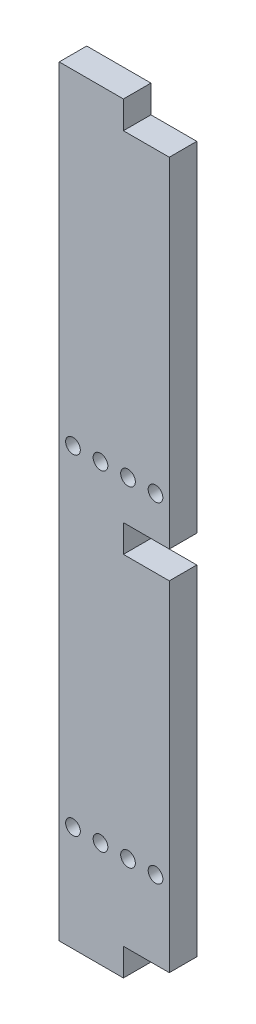
SolidWorks part; units mm, degrees
ref_plane "Plan de face" through (0, 0, 0) normal (0, 0, 1) x (1, 0, 0)
ref_plane "Plan de dessus" through (0, 0, 0) normal (0, 1, 0) x (1, 0, 0)
ref_plane "Plan de droite" through (0, 0, 0) normal (1, 0, 0) x (0, 0, -1)
sketch "Esquisse1" plane through (0, 0, 0) normal (0, 0, 1) x (1, 0, 0)
  line L0 (-6, 0) -> (6, 0)
  line L1 (6, 0) -> (6, 118) construction
  line L2 (6, 118) -> (-6, 118)
  line L3 (-6, 118) -> (-6, 0)
  line L4 (0, 118) -> (0, 0) construction
  line L10 (6, 100.5) -> (1, 100.5)
  line L11 (1, 100.5) -> (1, 97.5)
  line L12 (1, 97.5) -> (6, 97.5)
  line L13 (6, 97.5) -> (6, 60.5)
  line L14 (6, 60.5) -> (1, 60.5)
  line L15 (1, 60.5) -> (1, 57.5)
  line L16 (1, 57.5) -> (6, 57.5)
  line L17 (6, 57.5) -> (6, 20.5)
  line L18 (6, 20.5) -> (1, 20.5)
  line L19 (1, 20.5) -> (1, 17.5)
  line L20 (1, 17.5) -> (6, 17.5)
  line L25 (6, 17.5) -> (6, 0)
  line L26 (1, 99) -> (6, 99) construction
  line L27 (1, 59) -> (6, 59) construction
  line L28 (1, 19) -> (6, 19) construction
  line L32 (3.5, 298) -> (3.5, 99) construction
  line L33 (3.5, 99) -> (3.5, 59) construction
  line L34 (3.5, 59) -> (3.5, 19) construction
  line L35 (3.5, 19) -> (3.5, -180) construction
  line L36 (3.5, 298) -> (3.5, 118) construction
  line L38 (6, 118) -> (6, 100.5)
  point P8 (-1.034, 88.9537)
  point P9 (0, 65)
  point P10 (-1, 88.9537)
  point P11 (1, 88.9537)
  point P23 (1, 88.9537)
  point P24 (0, 0)
  point P25 (0, 29)
  point P33 (50.1188, 107.9044)
  point P34 (38.4285, 107.9044)
  point P46 (-0.4418, 19)
  circle B0 centre (0, 105) radius 1.5 construction
  circle B1 centre (0, 93) radius 1.5 construction
  line B2 (-9.0699, 99) -> (8.1862, 99) construction
  circle B3 centre (0, 65) radius 1.5 construction
  circle B4 centre (0, 53) radius 1.5 construction
  line B5 (-9.0699, 59) -> (8.1862, 59) construction
  circle B6 centre (0, 25) radius 1.5 construction
  circle B7 centre (0, 13) radius 1.5 construction
  line B8 (-9.0699, 19) -> (8.1862, 19) construction
  line B9 (-4.5, 65) -> (4.5, 65) construction
  circle B10 centre (-4.5, 65) radius 0.8
  circle B11 centre (-1.5, 65) radius 0.8
  circle B12 centre (1.5, 65) radius 0.8
  circle B13 centre (4.5, 65) radius 0.8
  line B14 (-4.5, 29) -> (4.5, 29) construction
  circle B15 centre (-4.5, 29) radius 0.8
  circle B16 centre (-1.5, 29) radius 0.8
  circle B17 centre (1.5, 29) radius 0.8
  circle B18 centre (4.5, 29) radius 0.8
  dimension "D6" = 6
  dimension "D1" = 40
  dimension "D2" = 17.5
  dimension "D3" = 3
  dimension "D4" = 12
  dimension "D5" = 5
  dimension "10" = 10
sketch_block_instance "Bloc1-2"
sketch_block "Bloc1" parameters "D1"=3, "D3"=3, "D2"=12
sketch_block_instance "Bloc1-3"
sketch_block_instance "Bloc1-5"
sketch_block_instance "Bloc2-2"
sketch_block "Bloc2" parameters "D4"=1.6, "D1"=3, "D2"=3, "D3"=3, "D5"=9
sketch_block_instance "Bloc2-3"
extrude "Boss.-Extru.1" add sketch "Esquisse1" along normal blind 3
sketch "Esquisse2" plane through (0, 0, 3) normal (0, 0, 1) x (1, 0, 0)
  line L1 (-6, 118) -> (6, 118)
  line L2 (-6, 118) -> (-6, 100.5)
  line L3 (-6, 100.5) -> (6, 100.5)
  line L4 (6, 118) -> (6, 100.5)
  line L5 (-6, 0) -> (6, 0)
  line L6 (-6, 0) -> (-6, 17.5)
  line L7 (-6, 17.5) -> (6, 17.5)
  line L8 (6, 0) -> (6, 17.5)
extrude "Enlèv. mat.-Extru.1" cut sketch "Esquisse2" against normal through all
